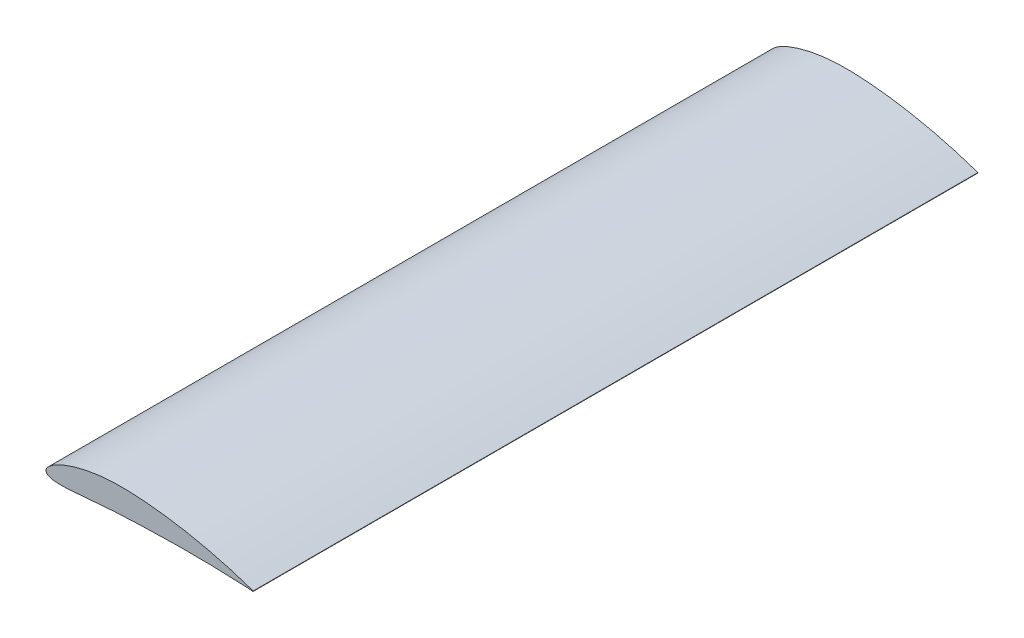
SolidWorks part; units mm, degrees
ref_plane "Front Plane" through (0, 0, 0) normal (0, 0, 1) x (1, 0, 0)
ref_plane "Top Plane" through (0, 0, 0) normal (0, 1, 0) x (1, 0, 0)
ref_plane "Right Plane" through (0, 0, 0) normal (1, 0, 0) x (0, 0, -1)
curve "Curve2"
  spline degree 3 poles (1000.25, 1.24, 0) (999.36, 1.5466, 0) (995.8139, 2.7683, 0) (987.8762, 5.5077, 0) (974.7136, 9.9275, 0) (956.465, 15.9446, 0) (933.2861, 23.3123, 0) (905.3935, 31.8009, 0) (873.0611, 41.1442, 0) (836.5996, 51.0483, 0) (796.3762, 61.2143, 0) (752.7953, 71.3209, 0) (706.3231, 81.1144, 0) (657.4446, 90.2776, 0) (606.6871, 98.541, 0) (554.6079, 105.6901, 0) (501.792, 111.4952, 0) (448.8062, 115.7722, 0) (395.8896, 118.5809, 0) (343.6082, 118.9114, 0) (292.6925, 116.357, 0) (244.199, 111.1728, 0) (198.7693, 103.6648, 0) (157.0012, 94.1608, 0) (119.4181, 83.1247, 0) (86.4596, 71.0512, 0) (58.48, 58.4287, 0) (35.7445, 45.7437, 0) (18.354, 33.4445, 0) (6.4016, 21.7983, 0) (-0.4785, 10.7687, 0) (-1.1021, -0.3322, 0) (5.4783, -9.2258, 0) (17.0143, -14.7948, 0) (32.8747, -18.4511, 0) (53.3085, -20.3675, 0) (78.1118, -20.7512, 0) (107.0475, -19.7633, 0) (139.7896, -17.6475, 0) (176.0022, -14.654, 0) (215.3329, -11.125, 0) (257.4273, -7.3624, 0) (301.9209, -3.6922, 0) (348.4441, -0.4557, 0) (396.9816, 1.9832, 0) (447.1013, 3.7059, 0) (498.2783, 5.4818, 0) (549.6221, 6.9005, 0) (600.5599, 7.9279, 0) (650.5484, 8.5041, 0) (699.0372, 8.6069, 0) (745.4858, 8.2663, 0) (789.3705, 7.5598, 0) (830.1852, 6.5089, 0) (867.4516, 5.2968, 0) (900.7439, 3.9432, 0) (929.5972, 2.6539, 0) (953.857, 1.2862, 0) (972.6764, 0.624, 0) (987.1696, -1.0584, 0) (994.3521, -0.0144, 0) (999.8798, -2.0481, 0) (999.9716, -0.4847, 0) (1000, 0, 0) knots 0 0 0 0 0.001372 0.005465 0.012235 0.021602 0.033461 0.047671 0.064081 0.082496 0.102719 0.124527 0.147676 0.171913 0.196978 0.222597 0.248497 0.274385 0.300041 0.32569 0.350525 0.37428 0.396711 0.417577 0.436654 0.453744 0.46868 0.481329 0.491631 0.499616 0.505546 0.510185 0.514824 0.520702 0.528516 0.538466 0.550543 0.564643 0.580638 0.598345 0.617584 0.638174 0.659922 0.682632 0.706121 0.730727 0.7557 0.780732 0.805564 0.829932 0.85357 0.876213 0.89761 0.917519 0.935698 0.951943 0.966047 0.97784 0.987174 0.993932 0.998018 0.999386 1 1 1 1
sketch "Sketch1" plane through (0, 0, 0) normal (0, 0, 1) x (1, 0, 0)
  arc A0 (1000.25, 1.24) -> (1000, 0) centre (1000.0422, 0.6367) cw
  spline S0 degree 3 poles (1071.3958, -1956.545) (1436.9332, -141.2985) (1213.3722, -72.3137) (987.8762, 5.5077) (974.7136, 9.9275) (956.465, 15.9446) (933.2861, 23.3123) (905.3935, 31.8009) (873.0611, 41.1442) (836.5996, 51.0483) (796.3762, 61.2143) (752.7953, 71.3209) (706.3231, 81.1144) (657.4446, 90.2776) (606.6871, 98.541) (554.6079, 105.6901) (501.792, 111.4952) (448.8062, 115.7722) (395.8896, 118.5809) (343.6082, 118.9114) (292.6925, 116.357) (244.199, 111.1728) (198.7693, 103.6648) (157.0012, 94.1608) (119.4181, 83.1247) (86.4596, 71.0512) (58.48, 58.4287) (35.7445, 45.7437) (18.354, 33.4445) (6.4016, 21.7983) (-0.4785, 10.7687) (-1.1021, -0.3322) (5.4783, -9.2258) (17.0143, -14.7948) (32.8747, -18.4511) (53.3085, -20.3675) (78.1118, -20.7512) (107.0475, -19.7633) (139.7896, -17.6475) (176.0022, -14.654) (215.3329, -11.125) (257.4273, -7.3624) (301.9209, -3.6922) (348.4441, -0.4557) (396.9816, 1.9832) (447.1013, 3.7059) (498.2783, 5.4818) (549.6221, 6.9005) (600.5599, 7.9279) (650.5484, 8.5041) (699.0372, 8.6069) (745.4858, 8.2663) (789.3705, 7.5598) (830.1852, 6.5089) (867.4516, 5.2968) (900.7439, 3.9432) (929.5972, 2.6539) (953.857, 1.2862) (972.6764, 0.624) (987.1696, -1.0584) (994.3521, -0.0144) (1010.8156, -6.0714) (938.1956, 100.2197) (2230.5974, -1569.3283) knots -0.335333 -0.335333 -0.335333 -0.335333 0.001372 0.005465 0.012235 0.021602 0.033461 0.047671 0.064081 0.082496 0.102719 0.124527 0.147676 0.171913 0.196978 0.222597 0.248497 0.274385 0.300041 0.32569 0.350525 0.37428 0.396711 0.417577 0.436654 0.453744 0.46868 0.481329 0.491631 0.499616 0.505546 0.510185 0.514824 0.520702 0.528516 0.538466 0.550543 0.564643 0.580638 0.598345 0.617584 0.638174 0.659922 0.682632 0.706121 0.730727 0.7557 0.780732 0.805564 0.829932 0.85357 0.876213 0.89761 0.917519 0.935698 0.951943 0.966047 0.97784 0.987174 0.993932 0.998018 0.999386 1.012006 1.012006 1.012006 1.012006 only from (1000.25, 1.24) to (1000, 0) construction
  spline S1 degree 3 poles (1000.25, 1.24) (999.36, 1.5466) (995.8139, 2.7683) (987.8762, 5.5077) (974.7136, 9.9275) (956.465, 15.9446) (933.2861, 23.3123) (905.3935, 31.8009) (873.0611, 41.1442) (836.5996, 51.0483) (796.3762, 61.2143) (752.7953, 71.3209) (706.3231, 81.1144) (657.4446, 90.2776) (606.6871, 98.541) (554.6079, 105.6901) (501.792, 111.4952) (448.8062, 115.7722) (395.8896, 118.5809) (343.6082, 118.9114) (292.6925, 116.357) (244.199, 111.1728) (198.7693, 103.6648) (157.0012, 94.1608) (119.4181, 83.1247) (86.4596, 71.0512) (58.48, 58.4287) (35.7445, 45.7437) (18.354, 33.4445) (6.4016, 21.7983) (-0.4785, 10.7687) (-1.1021, -0.3322) (5.4783, -9.2258) (17.0143, -14.7948) (32.8747, -18.4511) (53.3085, -20.3675) (78.1118, -20.7512) (107.0475, -19.7633) (139.7896, -17.6475) (176.0022, -14.654) (215.3329, -11.125) (257.4273, -7.3624) (301.9209, -3.6922) (348.4441, -0.4557) (396.9816, 1.9832) (447.1013, 3.7059) (498.2783, 5.4818) (549.6221, 6.9005) (600.5599, 7.9279) (650.5484, 8.5041) (699.0372, 8.6069) (745.4858, 8.2663) (789.3705, 7.5598) (830.1852, 6.5089) (867.4516, 5.2968) (900.7439, 3.9432) (929.5972, 2.6539) (953.857, 1.2862) (972.6764, 0.624) (987.1696, -1.0584) (994.3521, -0.0144) (999.8798, -2.0481) (999.9716, -0.4847) (1000, 0) knots 0 0 0 0 0.001372 0.005465 0.012235 0.021602 0.033461 0.047671 0.064081 0.082496 0.102719 0.124527 0.147676 0.171913 0.196978 0.222597 0.248497 0.274385 0.300041 0.32569 0.350525 0.37428 0.396711 0.417577 0.436654 0.453744 0.46868 0.481329 0.491631 0.499616 0.505546 0.510185 0.514824 0.520702 0.528516 0.538466 0.550543 0.564643 0.580638 0.598345 0.617584 0.638174 0.659922 0.682632 0.706121 0.730727 0.7557 0.780732 0.805564 0.829932 0.85357 0.876213 0.89761 0.917519 0.935698 0.951943 0.966047 0.97784 0.987174 0.993932 0.998018 0.999386 1 1 1 1
extrude "Boss-Extrude1" add sketch "Sketch1" along normal blind 7000 contours S1 A0
scale "Scale1" bodies to scale 101 scale about origin uniform scaling no x scale factor 2 y scale factor 2 z scale factor 1
